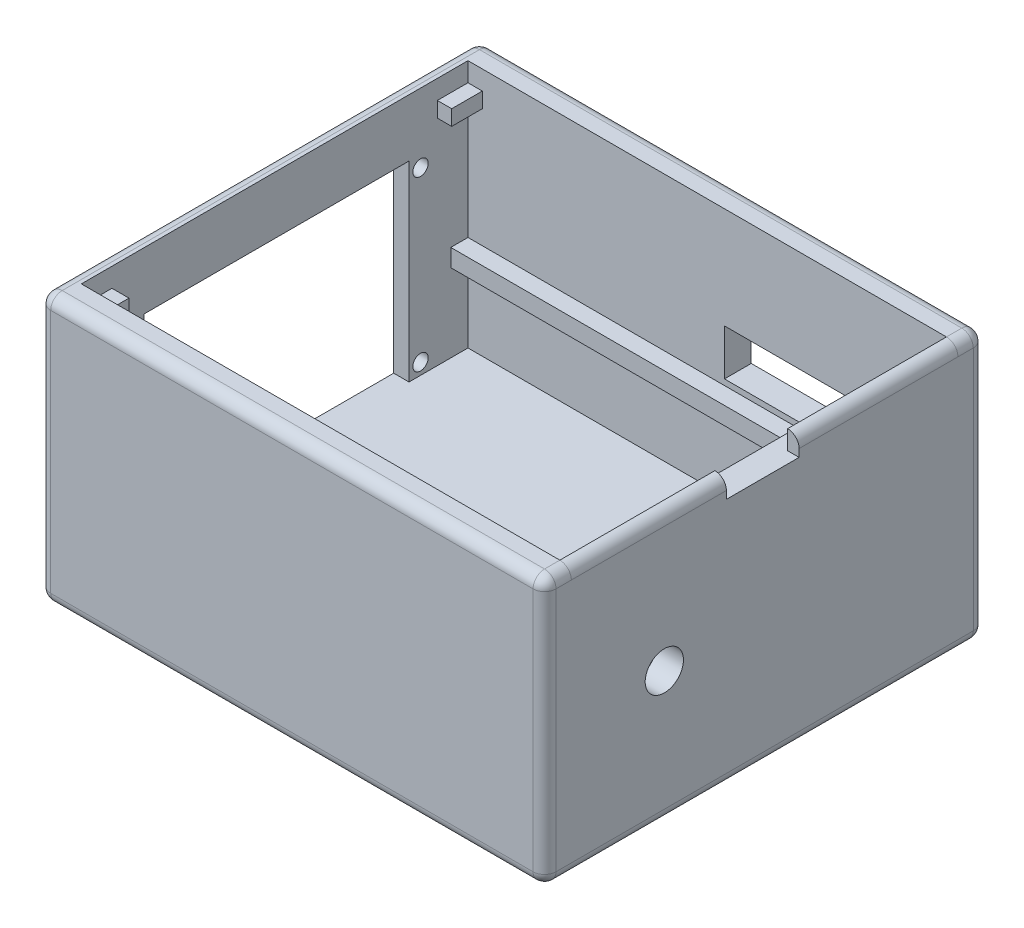
SolidWorks part; units mm, degrees
ref_plane "Front Plane" through (0, 0, 0) normal (0, 0, 1) x (1, 0, 0)
ref_plane "Top Plane" through (0, 0, 0) normal (0, 1, 0) x (1, 0, 0)
ref_plane "Right Plane" through (0, 0, 0) normal (1, 0, 0) x (0, 0, -1)
sketch "Sketch2" plane through (0, 0, 0) normal (0, 1, 0) x (1, 0, 0)
  line L0 (-60.5, 50.5) -> (-60.5, -50.5)
  line L1 (-67.5, 57.5) -> (67.5, 57.5)
  line L2 (-67.5, 57.5) -> (-67.5, -57.5)
  line L3 (-67.5, -57.5) -> (67.5, -57.5)
  line L4 (67.5, 57.5) -> (67.5, -57.5)
  line L5 (-67.5, 57.5) -> (67.5, -57.5) construction
  line L6 (-67.5, -57.5) -> (67.5, 57.5) construction
  line L7 (-60.5, -50.5) -> (60.5, -50.5)
  line L8 (60.5, 50.5) -> (60.5, -50.5)
  line L9 (-60.5, 50.5) -> (60.5, 50.5)
  point P0 (0, 0)
  dimension "D1" = 115
  dimension "D2" = 135
  dimension "D3" = 7
extrude "Boss-Extrude1" add sketch "Sketch2" along normal blind 70
extrude "Boss-Extrude2" add sketch "Sketch2<2>" along normal blind 5 contours L9 L0 L7 L8 region at (0, 0, 0)
sketch "Sketch2<2>" plane through (0, 0, 0) normal (0, 1, 0) x (1, 0, 0) same geometry as "Sketch2"
sketch "Sketch3" plane through (0, 0, -50.5) normal (0, 0, 1) x (1, 0, 0)
  line L1 (0, 0) -> (0, 70) construction
  line L2 (67.5, 0) -> (-67.5, 0) construction
  line L3 (60.5, 70) -> (-60.5, 70) construction
  line L4 (60.5, 70) -> (60.5, 5) construction
  line L5 (-60.5, 25.4157) -> (60.5, 25.4157)
  line L6 (-60.5, 25.4157) -> (-60.5, 30)
  line L7 (-60.5, 30) -> (60.5, 30)
  line L8 (60.5, 25.4157) -> (60.5, 30)
  line L9 (-60.5, 25.4157) -> (60.5, 30) construction
  line L10 (-60.5, 30) -> (60.5, 25.4157) construction
  line L11 (-60.5, 5) -> (60.5, 5) construction
  line L12 (-60.5, 70) -> (-60.5, 5) construction
  line L13 (6.5, 43.5) -> (39.5, 43.5)
  line L14 (6.5, 43.5) -> (6.5, 31.5)
  line L15 (6.5, 31.5) -> (39.5, 31.5)
  line L16 (39.5, 43.5) -> (39.5, 31.5)
  line L17 (6.5, 43.5) -> (39.5, 31.5) construction
  line L18 (6.5, 31.5) -> (39.5, 43.5) construction
  point P1 (0, 27.7078)
  point P16 (23, 37.5)
  dimension "D1" = 25
  dimension "D2" = 121
  dimension "D3" = 33
  dimension "D4" = 12
  dimension "D5" = 67
  dimension "D6" = 13.5
extrude "Boss-Extrude3" add sketch "Sketch3" along normal blind 4.5 contours L5 L8 L7 L6
extrude "Cut-Extrude1" cut sketch "Sketch3<3>" against normal through all contours L16 L13 L14 L15 region at (23, 37.5, -50.5)
sketch "Sketch3<3>" plane through (0, 0, -50.5) normal (0, 0, 1) x (1, 0, 0) same geometry as "Sketch3"
sketch "Sketch10" plane through (0, 0, 57.5) normal (0, 0, 1) x (1, 0, 0)
  circle A0 centre (-37.7153, 36.3262) radius 4.25
sketch "Sketch11" plane through (-67.5, 0, 0) normal (-1, 0, 0) x (0, 0, 1)
  line L0 (-57.5, 70) -> (-57.5, 0) construction
  line L1 (-41.1, 5) -> (39.9, 5)
  line L2 (-41.1, 5) -> (-41.1, 55)
  line L3 (-41.1, 55) -> (39.9, 55)
  line L4 (39.9, 5) -> (39.9, 55)
  line L7 (-35.1, 55) -> (34.1, 55)
  line L8 (-35.1, 55) -> (-35.1, 5)
  line L9 (-35.1, 5) -> (34.1, 5)
  line L14 (0, 0) -> (0, 70) construction
  line L15 (-57.5, 0) -> (57.5, 0) construction
  line L16 (-57.5, 70) -> (57.5, 70) construction
  line L19 (34.1, 55) -> (34.1, 5)
  line L21 (-41.1, 30) -> (39.9, 30) construction
  circle A4 centre (-38.1, 52) radius 2
  circle A5 centre (38.1, 52) radius 2
  circle A6 centre (38.1, 8) radius 2
  circle A7 centre (-38.1, 8) radius 2
  point P0 (0, 29.9383)
  dimension "D2" = 3
  dimension "D3" = 69.2
  dimension "D1" = 3
  dimension "D5" = 81
  dimension "D4" = 22.4
  dimension "D7" = 4
  dimension "D6" = 3
extrude "Cut-Extrude3" cut sketch "Sketch11" against normal blind 26.5 contours L19 L3 L8 L1 | A7 | A5 | A6 | A4 region at (-67.5, 30, -0.5) region at (-67.5, 8, 38.0642) region at (-67.5, 52, 38.0642) region at (-67.5, 8, -38.1)
sketch "Sketch12" plane through (0, 70, 0) normal (0, 1, 0) x (1, 0, 0)
  line L0 (67.5, -57.5) -> (67.5, 57.5) construction
  line L3 (60.5, -52.1714) -> (67.5, -52.1714)
  line L5 (60.5, 50.5) -> (67.5, 50.5)
  line L6 (60.5, 50.5) -> (60.5, -50.5)
  line L7 (60.5, -50.5) -> (67.5, -50.5)
  line L8 (67.5, 50.5) -> (67.5, -50.5)
  point P7 (60.5, -50)
  line M5 (67.5, -57.5) -> (67.5, 57.5)
  line M11 (60.5, 50.5) -> (60.5, -50.5)
sketch "Sketch21" plane through (67.5, 0, 0) normal (1, 0, 0) x (0, 0, -1)
  circle A0 centre (-26.2093, 34.3164) radius 5
extrude "Cut-Extrude7" cut sketch "Sketch21" against normal blind 10 contours A0
extrude "Cut-Extrude4" cut sketch "Sketch12" against normal blind 5 contours L7 L5 M11 M5 region at (64, 70, 0)
sketch "Sketch13" plane through (0, 60, 0) normal (0, 1, 0) x (1, 0, 0)
  line L1 (67.5, 45) -> (60.5, 45) construction
  line L5 (67.5, 45) -> (64, 45)
  line L7 (64, 45) -> (67.5, 45)
  line L8 (64, 45) -> (64, -50.5)
  line L9 (64, -50.5) -> (67.5, -50.5)
  line L10 (67.5, 45) -> (67.5, -50.5)
  point P1 (0, 0)
  point P4 (67.5, 45)
  point P5 (67.5, 45)
  point P6 (67.5, 45)
sketch "Sketch15" plane through (-67.5, 0, 0) normal (-1, 0, 0) x (0, 0, 1)
  line L1 (-57.5, 0) -> (57.5, 0)
  line L2 (-57.5, 0) -> (-57.5, 70)
  line L3 (-57.5, 70) -> (57.5, 70)
  line L4 (57.5, 0) -> (57.5, 70)
extrude "Cut-Extrude6" cut sketch "Sketch15" against normal blind 3
sketch "Sketch16" plane through (0, 5, 0) normal (0, 1, 0) x (1, 0, 0)
  line L0 (-60.5, 0) -> (60.5, 0) construction
  line L1 (-60.5, 50.5) -> (-60.5, -50.5) construction
  line L2 (60.5, 45) -> (60.5, -45) construction
sketch "Sketch17" plane through (0, 0, 50.5) normal (0, 0, -1) x (-1, 0, 0)
  line L0 (0, 0) -> (0, 70) construction
  line L1 (-60.3877, 30) -> (60.5375, 30)
  line L2 (-60.3877, 30) -> (-60.3877, 25.5)
  line L3 (-60.3877, 25.5) -> (60.5375, 25.5)
  line L4 (60.5375, 30) -> (60.5375, 25.5)
  line L5 (60.5, 70) -> (-67.5, 70) construction
  point P12 (0, 4.8129)
  dimension "D1" = 4.5
  dimension "D2" = 25.5
extrude "Boss-Extrude5" add sketch "Sketch17" along normal blind 4.5 contours L2 L1 L4 L3
sketch "Sketch18" plane through (0, 0, 0) normal (1, 0, 0) x (0, 0, -1)
fillet "Fillet1" radius 3 3 edges at (67.5, 0, 0) (1.5, 0, 57.5) (1.5, 0, -57.5)
fillet "Fillet2" radius 3 9 edges at (66.6213, 0.8787, -56.6213) (-64.5, 36.5, -57.5) (-64.5, 0.8787, -56.6213) (-64.5, 0, 0) (-64.5, 0.8787, 56.6213) (66.6213, 0.8787, 56.6213) (67.5, 36.5, -57.5) (-64.5, 36.5, 57.5) (67.5, 36.5, 57.5)
fillet "Fillet3" radius 3 9 edges at (67.5, 70, -52.5) (66.6213, 70, -56.6213) (1.5, 70, -57.5) (-63.6213, 70, -56.6213) (-64.5, 70, 0) (-63.6213, 70, 56.6213) (1.5, 70, 57.5) (66.6213, 70, 56.6213) (67.5, 70, 52.5)
sketch "Sketch22" plane through (0, 65, 0) normal (0, 1, 0) x (1, 0, 0)
  line L1 (64.5, 50.5) -> (67.5, 50.5)
  line L2 (64.5, 50.5) -> (64.5, -50.5)
  line L3 (64.5, -50.5) -> (67.5, -50.5)
  line L4 (67.5, 50.5) -> (67.5, -50.5)
extrude "Boss-Extrude8" add sketch "Sketch22" along normal blind 5
sketch "Sketch14" plane through (67.5, 0, 0) normal (1, 0, 0) x (0, 0, -1)
  line L0 (-10, 70) -> (9, 70)
  line L1 (-57.5, 70) -> (57.5, 70) construction
  line L2 (9, 70) -> (9, 65)
  line L3 (9, 65) -> (-10, 65)
  line L4 (-10, 65) -> (-10, 70)
  line L5 (-57.5, 70) -> (-57.5, 0) construction
  point P5 (-0.5, 70)
  dimension "D1" = 47.5
  dimension "D2" = 5
  dimension "D3" = 19
extrude "Cut-Extrude5" cut sketch "Sketch14" against normal blind 5
sketch "Sketch19" plane through (0, 0, -50.5) normal (0, 0, 1) x (1, 0, 0)
  line L0 (-60.5, 70) -> (-60.5, 30) construction
  line L1 (-60.5, 65) -> (-56.7558, 65)
  line L2 (-60.5, 65) -> (-60.5, 61)
  line L3 (-60.5, 61) -> (-56.7558, 61)
  line L4 (-56.7558, 65) -> (-56.7558, 61)
  dimension "D1" = 5
  dimension "D2" = 4
extrude "Boss-Extrude6" add sketch "Sketch19" along normal blind 8
sketch "Sketch20" plane through (0, 0, 50.5) normal (0, 0, -1) x (-1, 0, 0)
  line L0 (60.5, 70) -> (60.5, 30) construction
  line L1 (60.5, 65) -> (56.0522, 65)
  line L2 (60.5, 65) -> (60.5, 55.348)
  line L3 (60.5, 55.348) -> (56.0522, 55.348)
  line L4 (56.0522, 65) -> (56.0522, 55.348)
  dimension "D1" = 5
  dimension "D2" = 4.4478
extrude "Boss-Extrude7" add sketch "Sketch20" along normal blind 8
fillet "Fillet5" radius 3 1 edges at (67.5, 70, 30.25)
fillet "Fillet6" radius 3 1 edges at (67.5, 70, -29.75)
